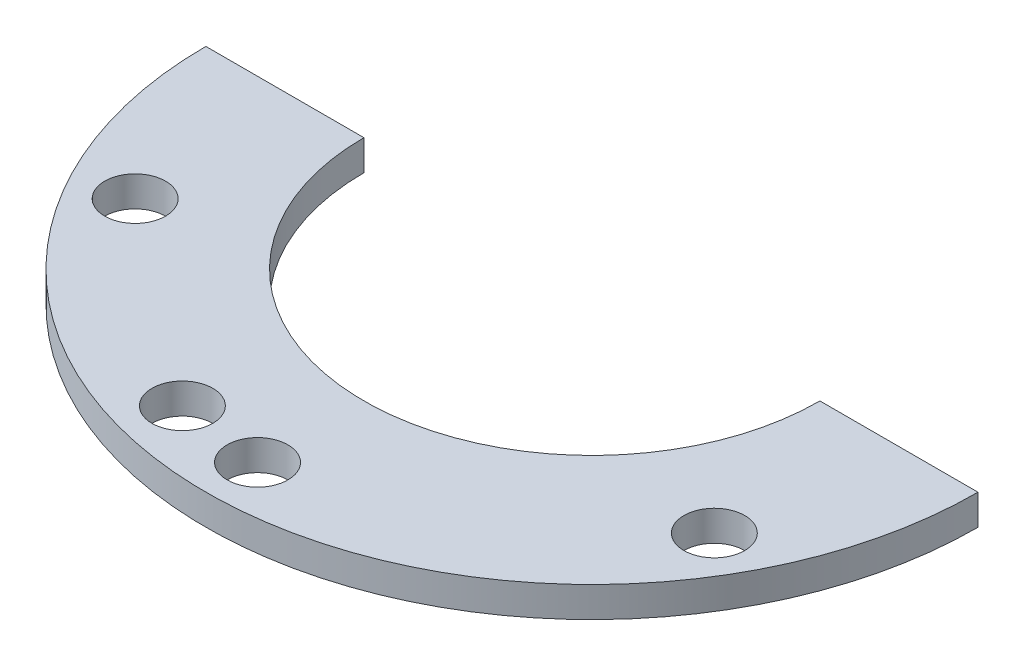
SolidWorks part; units mm, degrees
material "ABS"
ref_plane "Front Plane" through (0, 0, 0) normal (0, 0, 1) x (1, 0, 0)
ref_plane "Top Plane" through (0, 0, 0) normal (0, 1, 0) x (1, 0, 0)
ref_plane "Right Plane" through (0, 0, 0) normal (1, 0, 0) x (0, 0, -1)
sketch "Sketch1" plane through (0, 0, 0) normal (0, 1, 0) x (1, 0, 0)
  circle A0 centre (0, 0) radius 12.7
  dimension "D1" = 25.4
extrude "Boss-Extrude1" add sketch "Sketch1" along normal blind 1
sketch "Sketch19" plane through (0, 1, 0) normal (0, 1, 0) x (1, 0, 0)
  circle A0 centre (0, 11) radius 1
  circle A1 centre (9.5263, 5.5) radius 1
  circle A2 centre (9.5263, -5.5) radius 1
  circle A3 centre (0, -11) radius 1
  circle A4 centre (-9.5263, -5.5) radius 1
  circle A5 centre (-9.5263, 5.5) radius 1
  point P13 (0, 0)
  dimension "D1" = 2
  dimension "D2" = 11
  dimension "D3" = 6
extrude "Cut-Extrude1" cut sketch "Sketch19" against normal through all both and the other way through all
sketch "Sketch20" plane through (0, 1, 0) normal (0, 1, 0) x (1, 0, 0)
  circle A0 centre (0, 0) radius 7.5
  dimension "D1" = 15
extrude "Cut-Extrude2" cut sketch "Sketch20" against normal through all both and the other way through all
sketch "Sketch21" plane through (0, 0, 0) normal (0, 0, 1) x (1, 0, 0)
  line L1 (-36.7533, 32.3113) -> (29.1209, 32.3113)
  line L2 (-36.7533, 32.3113) -> (-36.7533, -19.668)
  line L3 (-36.7533, -19.668) -> (29.1209, -19.668)
  line L4 (29.1209, 32.3113) -> (29.1209, -19.668)
extrude "Cut-Extrude3" cut sketch "Sketch21" against normal through all
sketch "Sketch22" plane through (0, 1, 0) normal (0, 1, 0) x (1, 0, 0)
  line L0 (9.5263, -5.5) -> (0, -11)
  line L1 (0, 0) -> (4.7631, -8.25) construction
  line L2 (4.7631, -8.25) -> (0, 0) construction
  line L3 (0, 0) -> (-4.2868, -15.9987) construction
  circle A0 centre (-2.847, -10.6252) radius 1
  dimension "D1" = 2
  dimension "D2" = 11
  dimension "D3" = 45
extrude "Cut-Extrude4" cut sketch "Sketch22" against normal through all both and the other way through all contours A0 region at (-2.847, 1, 10.6252)
